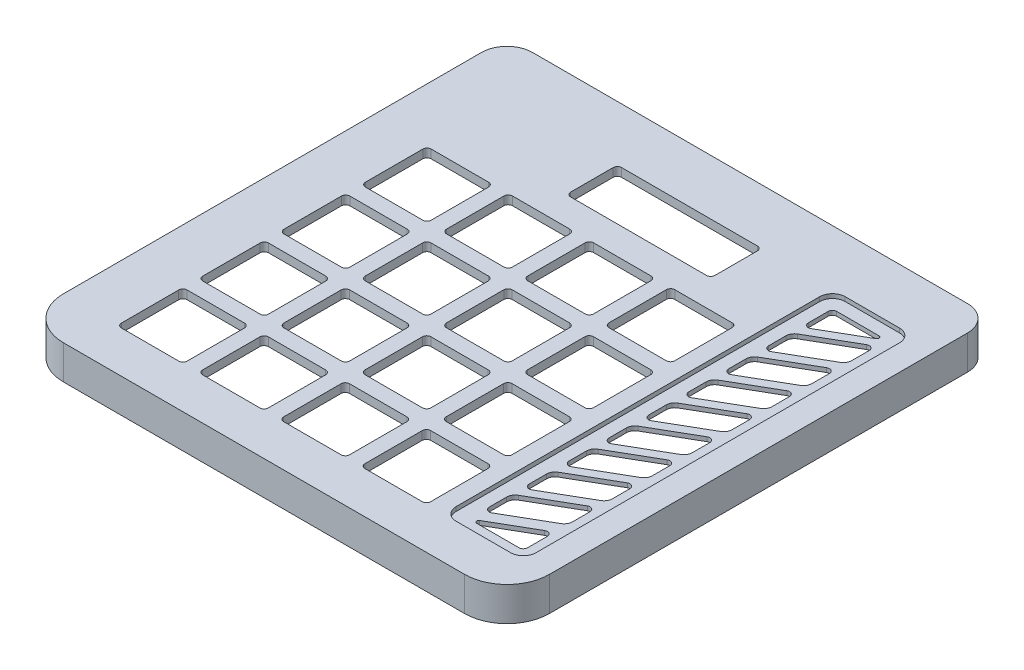
SolidWorks part; units mm, degrees
ref_plane "Plan de face" through (0, 0, 0) normal (0, 0, 1) x (1, 0, 0)
ref_plane "Plan de dessus" through (0, 0, 0) normal (0, 1, 0) x (1, 0, 0)
ref_plane "Plan de droite" through (0, 0, 0) normal (1, 0, 0) x (0, 0, -1)
sketch "Esquisse2" plane through (0, 0, 0) normal (0, 1, 0) x (1, 0, 0)
  line L1 (8, 0) -> (102.5, 0)
  line L2 (0, 8) -> (0, 106.5)
  line L3 (4, 110.5) -> (106.5, 110.5)
  line L4 (110.5, 8) -> (110.5, 106.5)
  line L5 (8, -2) -> (102.5, -2)
  line L6 (-2, 8) -> (-2, 106.5)
  line L7 (4, 112.5) -> (106.5, 112.5)
  line L8 (112.5, 8) -> (112.5, 106.5)
  arc A0 (0, 106.5) -> (4, 110.5) centre (4, 106.5) cw
  arc A1 (106.5, 110.5) -> (110.5, 106.5) centre (106.5, 106.5) cw
  arc A2 (102.5, 0) -> (110.5, 8) centre (102.5, 8) ccw
  arc A3 (8, 0) -> (0, 8) centre (8, 8) cw
  arc A4 (-2, 106.5) -> (4, 112.5) centre (4, 106.5) cw
  arc A5 (112.5, 106.5) -> (106.5, 112.5) centre (106.5, 106.5) ccw
  arc A6 (102.5, -2) -> (112.5, 8) centre (102.5, 8) ccw
  arc A7 (8, -2) -> (-2, 8) centre (8, 8) cw
  point P7 (0, 110.5)
  point P12 (110.5, 0)
  point P15 (0, 0)
  dimension "D3" = 4
  dimension "D4" = 8
  dimension "D9" = 6
  dimension "D10" = 6
  dimension "D11" = 10
  dimension "D1" = 110.5
  dimension "D2" = 110.5
  dimension "D5" = 2
  dimension "D6" = 2
  dimension "D7" = 2
  dimension "D8" = 2
extrude "Boss.-Extru.1" add sketch "Esquisse2" along normal blind 6
sketch "Esquisse3" plane through (0, 6, 0) normal (0, 1, 0) x (1, 0, 0)
  line L0 (-2, 106.5) -> (-2, 112.5) construction
  line L1 (4, 112.5) -> (-2, 112.5) construction
  line L2 (102.5, -2) -> (112.5, -2) construction
  line L3 (4, 112.5) -> (106.5, 112.5)
  line L4 (-2, 106.5) -> (-2, 8)
  line L5 (8, -2) -> (102.5, -2)
  line L6 (112.5, 106.5) -> (112.5, 8)
  line L7 (112.5, 8) -> (112.5, -2) construction
  arc A0 (106.5, 112.5) -> (112.5, 106.5) centre (106.5, 106.5) cw
  arc A1 (4, 112.5) -> (-2, 106.5) centre (4, 106.5) ccw
  arc A2 (102.5, -2) -> (112.5, 8) centre (102.5, 8) ccw
  arc A3 (-2, 8) -> (8, -2) centre (8, 8) ccw
  dimension "D1" = 6
  dimension "D2" = 10
extrude "Boss.-Extru.2" add sketch "Esquisse3" along normal blind 2
sketch "Esquisse5" plane through (0, 8, 0) normal (0, 1, 0) x (1, 0, 0)
  line L0 (112.5, 8) -> (112.5, 106.5) construction
  line L5 (-2, 106.5) -> (-2, 8) construction
  line L6 (38, 87.5) -> (70, 87.5)
  line L8 (11.8, 80.849) -> (25.3, 80.849)
  line L9 (10.8, 79.849) -> (10.8, 66.349)
  line L10 (11.8, 65.349) -> (25.3, 65.349)
  line L11 (26.3, 79.849) -> (26.3, 66.349)
  line L75 (29.9262, 79.849) -> (29.9262, 66.349)
  line L76 (30.9262, 80.849) -> (44.4262, 80.849)
  line L77 (45.4262, 79.849) -> (45.4262, 66.349)
  line L78 (30.9262, 65.349) -> (44.4262, 65.349)
  line L79 (49.0524, 79.849) -> (49.0524, 66.349)
  line L80 (50.0524, 80.849) -> (63.5524, 80.849)
  line L81 (64.5524, 79.849) -> (64.5524, 66.349)
  line L82 (50.0524, 65.349) -> (63.5524, 65.349)
  line L83 (68.1786, 79.849) -> (68.1786, 66.349)
  line L84 (69.1786, 80.849) -> (82.6786, 80.849)
  line L85 (83.6786, 79.849) -> (83.6786, 66.349)
  line L86 (69.1786, 65.349) -> (82.6786, 65.349)
  line L87 (29.9262, 60.6815) -> (29.9262, 47.1815)
  line L88 (30.9262, 61.6815) -> (44.4262, 61.6815)
  line L89 (45.4262, 60.6815) -> (45.4262, 47.1815)
  line L90 (30.9262, 46.1815) -> (44.4262, 46.1815)
  line L91 (49.0524, 60.6815) -> (49.0524, 47.1815)
  line L92 (50.0524, 61.6815) -> (63.5524, 61.6815)
  line L93 (64.5524, 60.6815) -> (64.5524, 47.1815)
  line L94 (50.0524, 46.1815) -> (63.5524, 46.1815)
  line L95 (68.1786, 60.6815) -> (68.1786, 47.1815)
  line L96 (69.1786, 61.6815) -> (82.6786, 61.6815)
  line L97 (83.6786, 60.6815) -> (83.6786, 47.1815)
  line L98 (69.1786, 46.1815) -> (82.6786, 46.1815)
  line L99 (29.9262, 41.514) -> (29.9262, 28.014)
  line L100 (30.9262, 42.514) -> (44.4262, 42.514)
  line L101 (45.4262, 41.514) -> (45.4262, 28.014)
  line L102 (30.9262, 27.014) -> (44.4262, 27.014)
  line L103 (49.0524, 41.514) -> (49.0524, 28.014)
  line L104 (50.0524, 42.514) -> (63.5524, 42.514)
  line L105 (64.5524, 41.514) -> (64.5524, 28.014)
  line L106 (50.0524, 27.014) -> (63.5524, 27.014)
  line L107 (68.1786, 41.514) -> (68.1786, 28.014)
  line L108 (69.1786, 42.514) -> (82.6786, 42.514)
  line L109 (83.6786, 41.514) -> (83.6786, 28.014)
  line L110 (69.1786, 27.014) -> (82.6786, 27.014)
  line L111 (29.9262, 22.3465) -> (29.9262, 8.8465)
  line L112 (30.9262, 23.3465) -> (44.4262, 23.3465)
  line L113 (45.4262, 22.3465) -> (45.4262, 8.8465)
  line L114 (30.9262, 7.8465) -> (44.4262, 7.8465)
  line L115 (49.0524, 22.3465) -> (49.0524, 8.8465)
  line L116 (50.0524, 23.3465) -> (63.5524, 23.3465)
  line L117 (64.5524, 22.3465) -> (64.5524, 8.8465)
  line L118 (50.0524, 7.8465) -> (63.5524, 7.8465)
  line L119 (68.1786, 22.3465) -> (68.1786, 8.8465)
  line L120 (69.1786, 23.3465) -> (82.6786, 23.3465)
  line L121 (83.6786, 22.3465) -> (83.6786, 8.8465)
  line L122 (69.1786, 7.8465) -> (82.6786, 7.8465)
  line L123 (10.8, 60.6815) -> (10.8, 47.1815)
  line L124 (11.8, 61.6815) -> (25.3, 61.6815)
  line L125 (26.3, 60.6815) -> (26.3, 47.1815)
  line L126 (11.8, 46.1815) -> (25.3, 46.1815)
  line L127 (10.8, 41.514) -> (10.8, 28.014)
  line L128 (11.8, 42.514) -> (25.3, 42.514)
  line L129 (26.3, 41.514) -> (26.3, 28.014)
  line L130 (11.8, 27.014) -> (25.3, 27.014)
  line L131 (10.8, 22.3465) -> (10.8, 8.8465)
  line L132 (11.8, 23.3465) -> (25.3, 23.3465)
  line L133 (26.3, 22.3465) -> (26.3, 8.8465)
  line L134 (11.8, 7.8465) -> (25.3, 7.8465)
  line L135 (106.5, 112.5) -> (4, 112.5) construction
  line L136 (37, 88.5) -> (37, 98.5)
  line L137 (38, 99.5) -> (70, 99.5)
  line L138 (71, 88.5) -> (71, 98.5)
  arc A0 (25.3, 65.349) -> (26.3, 66.349) centre (25.3, 66.349) ccw
  arc A1 (10.8, 66.349) -> (11.8, 65.349) centre (11.8, 66.349) ccw
  arc A2 (11.8, 80.849) -> (10.8, 79.849) centre (11.8, 79.849) ccw
  arc A3 (25.3, 80.849) -> (26.3, 79.849) centre (25.3, 79.849) cw
  arc A4 (30.9262, 80.849) -> (29.9262, 79.849) centre (30.9262, 79.849) ccw
  arc A5 (29.9262, 66.349) -> (30.9262, 65.349) centre (30.9262, 66.349) ccw
  arc A6 (44.4262, 80.849) -> (45.4262, 79.849) centre (44.4262, 79.849) cw
  arc A7 (44.4262, 65.349) -> (45.4262, 66.349) centre (44.4262, 66.349) ccw
  arc A8 (50.0524, 80.849) -> (49.0524, 79.849) centre (50.0524, 79.849) ccw
  arc A9 (49.0524, 66.349) -> (50.0524, 65.349) centre (50.0524, 66.349) ccw
  arc A10 (63.5524, 80.849) -> (64.5524, 79.849) centre (63.5524, 79.849) cw
  arc A11 (63.5524, 65.349) -> (64.5524, 66.349) centre (63.5524, 66.349) ccw
  arc A12 (69.1786, 80.849) -> (68.1786, 79.849) centre (69.1786, 79.849) ccw
  arc A13 (68.1786, 66.349) -> (69.1786, 65.349) centre (69.1786, 66.349) ccw
  arc A14 (82.6786, 80.849) -> (83.6786, 79.849) centre (82.6786, 79.849) cw
  arc A15 (82.6786, 65.349) -> (83.6786, 66.349) centre (82.6786, 66.349) ccw
  arc A16 (30.9262, 61.6815) -> (29.9262, 60.6815) centre (30.9262, 60.6815) ccw
  arc A17 (29.9262, 47.1815) -> (30.9262, 46.1815) centre (30.9262, 47.1815) ccw
  arc A18 (44.4262, 61.6815) -> (45.4262, 60.6815) centre (44.4262, 60.6815) cw
  arc A19 (44.4262, 46.1815) -> (45.4262, 47.1815) centre (44.4262, 47.1815) ccw
  arc A20 (50.0524, 61.6815) -> (49.0524, 60.6815) centre (50.0524, 60.6815) ccw
  arc A21 (49.0524, 47.1815) -> (50.0524, 46.1815) centre (50.0524, 47.1815) ccw
  arc A22 (63.5524, 61.6815) -> (64.5524, 60.6815) centre (63.5524, 60.6815) cw
  arc A23 (63.5524, 46.1815) -> (64.5524, 47.1815) centre (63.5524, 47.1815) ccw
  arc A24 (69.1786, 61.6815) -> (68.1786, 60.6815) centre (69.1786, 60.6815) ccw
  arc A25 (68.1786, 47.1815) -> (69.1786, 46.1815) centre (69.1786, 47.1815) ccw
  arc A26 (82.6786, 61.6815) -> (83.6786, 60.6815) centre (82.6786, 60.6815) cw
  arc A27 (82.6786, 46.1815) -> (83.6786, 47.1815) centre (82.6786, 47.1815) ccw
  arc A28 (30.9262, 42.514) -> (29.9262, 41.514) centre (30.9262, 41.514) ccw
  arc A29 (29.9262, 28.014) -> (30.9262, 27.014) centre (30.9262, 28.014) ccw
  arc A30 (44.4262, 42.514) -> (45.4262, 41.514) centre (44.4262, 41.514) cw
  arc A31 (44.4262, 27.014) -> (45.4262, 28.014) centre (44.4262, 28.014) ccw
  arc A32 (50.0524, 42.514) -> (49.0524, 41.514) centre (50.0524, 41.514) ccw
  arc A33 (49.0524, 28.014) -> (50.0524, 27.014) centre (50.0524, 28.014) ccw
  arc A34 (63.5524, 42.514) -> (64.5524, 41.514) centre (63.5524, 41.514) cw
  arc A35 (63.5524, 27.014) -> (64.5524, 28.014) centre (63.5524, 28.014) ccw
  arc A36 (69.1786, 42.514) -> (68.1786, 41.514) centre (69.1786, 41.514) ccw
  arc A37 (68.1786, 28.014) -> (69.1786, 27.014) centre (69.1786, 28.014) ccw
  arc A38 (82.6786, 42.514) -> (83.6786, 41.514) centre (82.6786, 41.514) cw
  arc A39 (82.6786, 27.014) -> (83.6786, 28.014) centre (82.6786, 28.014) ccw
  arc A40 (30.9262, 23.3465) -> (29.9262, 22.3465) centre (30.9262, 22.3465) ccw
  arc A41 (29.9262, 8.8465) -> (30.9262, 7.8465) centre (30.9262, 8.8465) ccw
  arc A42 (44.4262, 23.3465) -> (45.4262, 22.3465) centre (44.4262, 22.3465) cw
  arc A43 (44.4262, 7.8465) -> (45.4262, 8.8465) centre (44.4262, 8.8465) ccw
  arc A44 (50.0524, 23.3465) -> (49.0524, 22.3465) centre (50.0524, 22.3465) ccw
  arc A45 (49.0524, 8.8465) -> (50.0524, 7.8465) centre (50.0524, 8.8465) ccw
  arc A46 (63.5524, 23.3465) -> (64.5524, 22.3465) centre (63.5524, 22.3465) cw
  arc A47 (63.5524, 7.8465) -> (64.5524, 8.8465) centre (63.5524, 8.8465) ccw
  arc A48 (69.1786, 23.3465) -> (68.1786, 22.3465) centre (69.1786, 22.3465) ccw
  arc A49 (68.1786, 8.8465) -> (69.1786, 7.8465) centre (69.1786, 8.8465) ccw
  arc A50 (82.6786, 23.3465) -> (83.6786, 22.3465) centre (82.6786, 22.3465) cw
  arc A51 (82.6786, 7.8465) -> (83.6786, 8.8465) centre (82.6786, 8.8465) ccw
  arc A52 (11.8, 61.6815) -> (10.8, 60.6815) centre (11.8, 60.6815) ccw
  arc A53 (10.8, 47.1815) -> (11.8, 46.1815) centre (11.8, 47.1815) ccw
  arc A54 (25.3, 61.6815) -> (26.3, 60.6815) centre (25.3, 60.6815) cw
  arc A55 (25.3, 46.1815) -> (26.3, 47.1815) centre (25.3, 47.1815) ccw
  arc A56 (11.8, 42.514) -> (10.8, 41.514) centre (11.8, 41.514) ccw
  arc A57 (10.8, 28.014) -> (11.8, 27.014) centre (11.8, 28.014) ccw
  arc A58 (25.3, 42.514) -> (26.3, 41.514) centre (25.3, 41.514) cw
  arc A59 (25.3, 27.014) -> (26.3, 28.014) centre (25.3, 28.014) ccw
  arc A60 (11.8, 23.3465) -> (10.8, 22.3465) centre (11.8, 22.3465) ccw
  arc A61 (10.8, 8.8465) -> (11.8, 7.8465) centre (11.8, 8.8465) ccw
  arc A62 (25.3, 23.3465) -> (26.3, 22.3465) centre (25.3, 22.3465) cw
  arc A63 (25.3, 7.8465) -> (26.3, 8.8465) centre (25.3, 8.8465) ccw
  arc A66 (38, 87.5) -> (37, 88.5) centre (38, 88.5) cw
  arc A67 (70, 87.5) -> (71, 88.5) centre (70, 88.5) ccw
  arc A68 (70, 99.5) -> (71, 98.5) centre (70, 98.5) cw
  arc A69 (37, 98.5) -> (38, 99.5) centre (38, 98.5) cw
  point P82 (10.8, 65.349)
  point P85 (10.8, 80.849)
  point P88 (26.3, 80.849)
  dimension "D10" = 1
  dimension "D17" = 1
  dimension "D2" = 3.6262
  dimension "D3" = 3.6675
  dimension "D4" = 31.651
  dimension "D5" = 12.8
  dimension "D6" = 15.5
  dimension "D7" = 15.5
  dimension "D8" = 4
  dimension "D18" = 13
  dimension "D19" = 41.5
  dimension "D20" = 34
  dimension "D21" = 12
  dimension "D9" = 4
extrude "Enlèv. mat.-Extru.1" cut sketch "Esquisse5" against normal blind 33 contours A3 L8 A2 L9 A1 L10 A0 L11 | L78 A7 L77 A6 L76 A4 L75 A5 | L82 A11 L81 A10 L80 A8 L79 A9 | L86 A15 L85 A14 L84 A12 L83 A13 | L98 A27 L97 A26 L96 A24 L95 A25 | L94 A23 L93 A22 L92 A20 L91 A21 | L90 A19 L89 A18 L88 A16 L87 A17 | L126 A55 L125 A54 L124 A52 L123 A53 | L130 A59 L129 A58 L128 A56 L127 A57 | L102 A31 L101 A30 L100 A28 L99 A29 | L106 A35 L105 A34 L104 A32 L103 A33 | L110 A39 L109 A38 L108 A36 L107 A37 | L122 A51 L121 A50 L120 A48 L119 A49 | L118 A47 L117 A46 L116 A44 L115 A45 | L114 A43 L113 A42 L112 A40 L111 A41 | L134 A63 L133 A62 L132 A60 L131 A61 | A69 L137 A68 L138 A67 L6 A66 L136 region at (18.55, 8, -73.099) region at (37.6762, 8, -73.099) region at (56.8024, 8, -73.099) region at (75.9286, 8, -73.099) region at (37.6762, 8, -53.9315) region at (56.8024, 8, -53.9315) region at (75.9286, 8, -53.9315) region at (37.6762, 8, -34.764) region at (56.8024, 8, -34.764) region at (75.9286, 8, -34.764) region at (37.6762, 8, -15.5965) region at (56.8024, 8, -15.5965) region at (75.9286, 8, -15.5965) region at (18.55, 8, -53.9315) region at (18.55, 8, -34.764) region at (18.55, 8, -15.5965)
sketch "Esquisse6" plane through (0, 8, 0) normal (0, 1, 0) x (1, 0, 0)
  line L0 (83.6786, 79.849) -> (83.6786, 66.349) construction
  line L1 (90.6786, 99.5) -> (103.5, 99.5)
  line L2 (87.6786, 96.5) -> (87.6786, 10.8465)
  line L3 (90.6786, 7.8465) -> (103.5, 7.8465)
  line L4 (106.5, 96.5) -> (106.5, 10.8465)
  line L5 (112.5, 8) -> (112.5, 106.5) construction
  line L6 (91.6786, 87.2749) -> (102, 93.234)
  line L7 (103.5, 92.3679) -> (103.5, 88.2547)
  line L8 (102.5, 86.5226) -> (92.1786, 80.5636)
  line L9 (69.1786, 7.8465) -> (82.6786, 7.8465) construction
  line L10 (38, 99.5) -> (70, 99.5) construction
  line L11 (90.6786, 95.5) -> (90.6786, 90.8296)
  line L12 (92.1786, 89.9636) -> (101.884, 95.567)
  line L13 (101.634, 96.5) -> (91.6786, 96.5)
  line L14 (102.5, 10.8465) -> (92.5446, 10.8465)
  line L15 (92.2946, 11.7795) -> (102, 17.3829)
  line L16 (103.5, 16.5169) -> (103.5, 11.8465)
  line L17 (90.6786, 96.5) -> (90.6786, 10.8465) construction
  line L18 (103.5, 10.8465) -> (103.5, 96.5) construction
  line L19 (90.6786, 81.4296) -> (90.6786, 85.5429)
  line L20 (90.6786, 72.0296) -> (90.6786, 76.1429)
  line L21 (91.6786, 77.8749) -> (102, 83.834)
  line L22 (103.5, 82.9679) -> (103.5, 78.8547)
  line L23 (102.5, 77.1226) -> (92.1786, 71.1636)
  line L24 (90.6786, 62.6296) -> (90.6786, 66.7429)
  line L25 (91.6786, 68.4749) -> (102, 74.434)
  line L26 (103.5, 73.5679) -> (103.5, 69.4547)
  line L27 (102.5, 67.7226) -> (92.1786, 61.7636)
  line L28 (90.6786, 53.2296) -> (90.6786, 57.3429)
  line L29 (91.6786, 59.0749) -> (102, 65.034)
  line L30 (103.5, 64.1679) -> (103.5, 60.0547)
  line L31 (102.5, 58.3226) -> (92.1786, 52.3636)
  line L32 (90.6786, 43.8296) -> (90.6786, 47.9429)
  line L33 (91.6786, 49.6749) -> (102, 55.634)
  line L34 (103.5, 54.7679) -> (103.5, 50.6547)
  line L35 (102.5, 48.9226) -> (92.1786, 42.9636)
  line L36 (90.6786, 34.4296) -> (90.6786, 38.5429)
  line L37 (91.6786, 40.2749) -> (102, 46.234)
  line L38 (103.5, 45.3679) -> (103.5, 41.2547)
  line L39 (102.5, 39.5226) -> (92.1786, 33.5636)
  line L40 (90.6786, 25.0296) -> (90.6786, 29.1429)
  line L41 (91.6786, 30.8749) -> (102, 36.834)
  line L42 (103.5, 35.9679) -> (103.5, 31.8547)
  line L43 (102.5, 30.1226) -> (92.1786, 24.1636)
  line L44 (90.6786, 15.6296) -> (90.6786, 19.7429)
  line L45 (91.6786, 21.4749) -> (102, 27.434)
  line L46 (103.5, 26.5679) -> (103.5, 22.4547)
  line L47 (102.5, 20.7226) -> (92.1786, 14.7636)
  arc A0 (103.5, 7.8465) -> (106.5, 10.8465) centre (103.5, 10.8465) ccw
  arc A1 (87.6786, 10.8465) -> (90.6786, 7.8465) centre (90.6786, 10.8465) ccw
  arc A2 (103.5, 99.5) -> (106.5, 96.5) centre (103.5, 96.5) cw
  arc A3 (90.6786, 99.5) -> (87.6786, 96.5) centre (90.6786, 96.5) ccw
  arc A4 (102, 27.434) -> (103.5, 26.5679) centre (102.5, 26.5679) cw
  arc A5 (90.6786, 15.6296) -> (92.1786, 14.7636) centre (91.6786, 15.6296) ccw
  arc A6 (90.6786, 25.0296) -> (92.1786, 24.1636) centre (91.6786, 25.0296) ccw
  arc A7 (102, 36.834) -> (103.5, 35.9679) centre (102.5, 35.9679) cw
  arc A8 (90.6786, 34.4296) -> (92.1786, 33.5636) centre (91.6786, 34.4296) ccw
  arc A9 (102, 46.234) -> (103.5, 45.3679) centre (102.5, 45.3679) cw
  arc A10 (102, 55.634) -> (103.5, 54.7679) centre (102.5, 54.7679) cw
  arc A11 (90.6786, 43.8296) -> (92.1786, 42.9636) centre (91.6786, 43.8296) ccw
  arc A12 (90.6786, 53.2296) -> (92.1786, 52.3636) centre (91.6786, 53.2296) ccw
  arc A13 (102, 65.034) -> (103.5, 64.1679) centre (102.5, 64.1679) cw
  arc A14 (90.6786, 62.6296) -> (92.1786, 61.7636) centre (91.6786, 62.6296) ccw
  arc A15 (102, 74.434) -> (103.5, 73.5679) centre (102.5, 73.5679) cw
  arc A16 (102, 83.834) -> (103.5, 82.9679) centre (102.5, 82.9679) cw
  arc A17 (90.6786, 72.0296) -> (92.1786, 71.1636) centre (91.6786, 72.0296) ccw
  arc A18 (92.1786, 80.5636) -> (90.6786, 81.4296) centre (91.6786, 81.4296) cw
  arc A19 (102, 93.234) -> (103.5, 92.3679) centre (102.5, 92.3679) cw
  arc A20 (90.6786, 19.7429) -> (91.6786, 21.4749) centre (92.6786, 19.7429) cw
  arc A21 (103.5, 22.4547) -> (102.5, 20.7226) centre (101.5, 22.4547) cw
  arc A22 (103.5, 31.8547) -> (102.5, 30.1226) centre (101.5, 31.8547) cw
  arc A23 (90.6786, 29.1429) -> (91.6786, 30.8749) centre (92.6786, 29.1429) cw
  arc A24 (103.5, 41.2547) -> (102.5, 39.5226) centre (101.5, 41.2547) cw
  arc A25 (90.6786, 38.5429) -> (91.6786, 40.2749) centre (92.6786, 38.5429) cw
  arc A26 (103.5, 50.6547) -> (102.5, 48.9226) centre (101.5, 50.6547) cw
  arc A27 (90.6786, 47.9429) -> (91.6786, 49.6749) centre (92.6786, 47.9429) cw
  arc A28 (103.5, 60.0547) -> (102.5, 58.3226) centre (101.5, 60.0547) cw
  arc A29 (90.6786, 57.3429) -> (91.6786, 59.0749) centre (92.6786, 57.3429) cw
  arc A30 (103.5, 88.2547) -> (102.5, 86.5226) centre (101.5, 88.2547) cw
  arc A31 (91.6786, 87.2749) -> (90.6786, 85.5429) centre (92.6786, 85.5429) ccw
  arc A32 (103.5, 78.8547) -> (102.5, 77.1226) centre (101.5, 78.8547) cw
  arc A33 (90.6786, 76.1429) -> (91.6786, 77.8749) centre (92.6786, 76.1429) cw
  arc A34 (90.6786, 66.7429) -> (91.6786, 68.4749) centre (92.6786, 66.7429) cw
  arc A35 (103.5, 69.4547) -> (102.5, 67.7226) centre (101.5, 69.4547) cw
  arc A36 (101.884, 95.567) -> (101.634, 96.5) centre (101.634, 96) ccw
  arc A37 (92.5446, 10.8465) -> (92.2946, 11.7795) centre (92.5446, 11.3465) cw
  arc A38 (102.5, 10.8465) -> (103.5, 11.8465) centre (102.5, 11.8465) ccw
  arc A39 (102, 17.3829) -> (103.5, 16.5169) centre (102.5, 16.5169) cw
  arc A40 (90.6786, 90.8296) -> (92.1786, 89.9636) centre (91.6786, 90.8296) ccw
  arc A41 (90.6786, 95.5) -> (91.6786, 96.5) centre (91.6786, 95.5) cw
  point P84 (90.6786, 79.6976)
  point P87 (103.5, 94.1)
  point P110 (103.5, 87.1)
  point P113 (90.6786, 86.6976)
  point P135 (90.6786, 89.0976)
  dimension "D3" = 3
  dimension "D11" = 1
  dimension "D12" = 2
  dimension "D13" = 0.5
  dimension "D14" = 1
  dimension "D1" = 4
  dimension "D2" = 6
  dimension "D4" = 30
  dimension "D5" = 30
  dimension "D6" = 2.4
  dimension "D7" = 2.4
  dimension "D8" = 7
  dimension "D9" = 8
  dimension "D10" = 2.0785
extrude "Enlèv. mat.-Extru.2" cut sketch "Esquisse6" against normal blind 2 contours L12 L13 L11 | L23 L22 L21 L20 | L27 L26 L25 L24 | L31 L30 L29 L28 | L35 L34 L33 L32 | L39 L38 L37 L36 | L43 L42 L41 L40 | L47 L46 L45 L44 | L16 L15 L14 | L19 A31 L6 A19 L7 A30 L8 A18 region at (94.9297, 8, -94.057) region at (99.2489, 8, -13.2895) region at (97.0893, 8, -77.4988) region at (97.0893, 8, -68.0988) region at (97.0893, 8, -58.6988) region at (97.0893, 8, -49.2988) region at (97.0893, 8, -39.8988) region at (97.0893, 8, -30.4988) region at (97.0893, 8, -21.0988)
extrude "Enlèv. mat.-Extru.3" cut sketch "Esquisse6<3>" against normal blind 1
sketch "Esquisse6<3>" plane through (0, 8, 0) normal (0, 1, 0) x (1, 0, 0) same geometry as "Esquisse6"
sketch "Esquisse10" plane through (0, 0, -112.5) normal (0, 0, -1) x (-1, 0, 0)
  line L0 (-106.5, 0) -> (-4, 0) construction
  line L1 (-99.75, 0) -> (-83.75, 0)
  line L2 (-99.75, 0) -> (-99.75, 2)
  line L3 (-97.75, 4) -> (-85.75, 4)
  line L4 (-83.75, 0) -> (-83.75, 2)
  line L5 (-112.5, 8) -> (-112.5, 0) construction
  arc A0 (-85.75, 4) -> (-83.75, 2) centre (-85.75, 2) cw
  arc A1 (-99.75, 2) -> (-97.75, 4) centre (-97.75, 2) cw
  point P10 (-83.75, 4)
  point P13 (-99.75, 4)
  dimension "D4" = 2
  dimension "D1" = 12.75
  dimension "D2" = 16
  dimension "D3" = 4
extrude "Enlèv. mat.-Extru.5" cut sketch "Esquisse10" against normal blind 2
